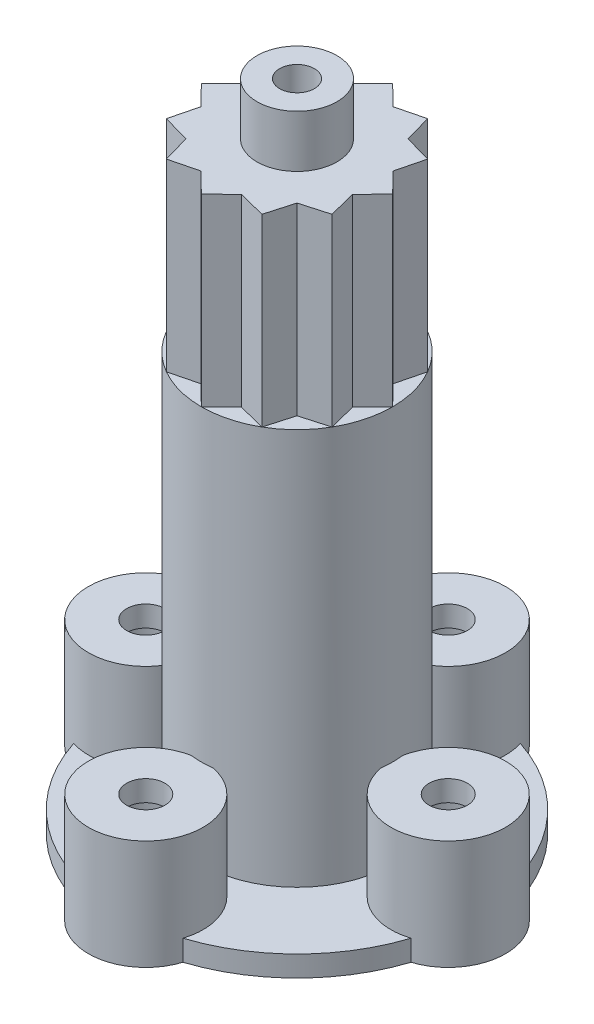
SolidWorks part; units mm, degrees
ref_plane "Front Plane" through (0, 0, 0) normal (0, 0, 1) x (1, 0, 0)
ref_plane "Top Plane" through (0, 0, 0) normal (0, 1, 0) x (1, 0, 0)
ref_plane "Right Plane" through (0, 0, 0) normal (1, 0, 0) x (0, 0, -1)
sketch "Sketch1" plane through (0, 0, 0) normal (0, 1, 0) x (1, 0, 0)
  circle A0 centre (0, 0) radius 10.2
  dimension "D1" = 20.4
extrude "Boss-Extrude1" add sketch "Sketch1" along normal blind 1.2
sketch "Sketch3" plane through (0, 1.2, 0) normal (0, 1, 0) x (1, 0, 0)
  circle A0 centre (0, 0) radius 5.5
  dimension "D1" = 11
extrude "Boss-Extrude2" add sketch "Sketch3" along normal blind 22.8
sketch "Sketch6" plane through (0, 0, 0) normal (0, -1, 0) x (1, 0, 0)
  line L0 (12.265, 0) -> (-12.265, 0) construction
  circle A0 centre (8.7, 0) radius 3.3
  dimension "D1" = 6.6
extrude "Boss-Extrude7" add sketch "Sketch6" against normal blind 6.3 contours A0
ref_axis "Axis1" through (0, 25.2, 0) along (0, -1, 0)
sketch "Sketch7" plane through (0, 0, 0) normal (0, -1, 0) x (1, 0, 0)
  circle A0 centre (8.7, 0) radius 2.2
  dimension "D1" = 4.4
extrude "Cut-Extrude1" cut sketch "Sketch7" against normal blind 5.1
sketch "Sketch8" plane through (0, 6.3, 0) normal (0, 1, 0) x (1, 0, 0)
  circle A0 centre (8.7, 0) radius 1.1
  dimension "D1" = 2.2
extrude "Cut-Extrude2" cut sketch "Sketch8" against normal blind 1.2
pattern_circular "CirPattern1" count 4 over 360 about axis through (0, 25.2, 0) along (0, -1, 0) of "Boss-Extrude7", "Cut-Extrude1", "Cut-Extrude2"
sketch "Sketch9" plane through (0, 0, 0) normal (0, -1, 0) x (-1, 0, 0)
  circle A0 centre (0, 0) radius 4.4
  dimension "D1" = 8.8
extrude "Cut-Extrude3" cut sketch "Sketch9" against normal blind 22.8
sketch "Sketch10" plane through (0, 24, 0) normal (0, 1, 0) x (1, 0, 0)
  circle A0 centre (0, 0) radius 4.5
  dimension "D1" = 9
extrude "Boss-Extrude8" add sketch "Sketch10" along normal blind 10.6
sketch "Sketch11" plane through (0, 24, 0) normal (0, 1, 0) x (1, 0, 0)
  line L0 (-1.2, 4.337) -> (1.2, 4.337)
  line L1 (1.2, 4.337) -> (0, 5.5)
  line L2 (0, 5.5) -> (-1.2, 4.337)
  line L3 (1.2, -4.337) -> (-1.2, -4.337) construction
  line L4 (1.2, -4.337) -> (1.2, 4.337) construction
  line L5 (1.2, 4.337) -> (-1.2, 4.337) construction
  line L6 (-1.2, -4.337) -> (-1.2, 4.337) construction
  line L7 (1.2, -4.337) -> (-1.2, 4.337) construction
  line L8 (1.2, 4.337) -> (-1.2, -4.337) construction
  circle A0 centre (0, 0) radius 4.5 construction
  arc A1 (0.6399, 5.4626) -> (-0.6399, 5.4626) centre (0, 0) ccw construction
  point P4 (0, 0)
  dimension "D1" = 2.4
extrude "Boss-Extrude9" add sketch "Sketch11" along normal blind 10.6 contours L2 L0 L1
pattern_circular "CirPattern2" count 12 over 360 about axis through (0, 25.2, 0) along (0, -1, 0) of "Boss-Extrude9"
sketch "Sketch12" plane through (0, 22.8, 0) normal (0, -1, 0) x (1, 0, 0)
  circle A0 centre (0, 0) radius 3.2
  dimension "D1" = 6.4
extrude "Cut-Extrude4" cut sketch "Sketch12" against normal blind 10.6
sketch "Sketch13" plane through (0, 34.6, 0) normal (0, 1, 0) x (1, 0, 0)
  circle A0 centre (0, 0) radius 2.3
  dimension "D1" = 4.6
extrude "Boss-Extrude10" add sketch "Sketch13" along normal blind 3
sketch "Sketch14" plane through (0, 37.6, 0) normal (0, 1, 0) x (1, 0, 0)
  circle A0 centre (0, 0) radius 1
  dimension "D1" = 2
extrude "Cut-Extrude5" cut sketch "Sketch14" against normal blind 3
sketch "Sketch15" plane through (0, 1.2, 0) normal (0, 1, 0) x (1, 0, 0)
  line L0 (-8.7, 0) -> (0, -8.7) construction
  line L1 (-5.0343, -3.6657) -> (-3.5963, -5.1037)
  line L2 (-5.0343, -3.6657) -> (-5.1861, -3.8174)
  line L3 (-3.5963, -5.1037) -> (-3.748, -5.2554)
  line L4 (-5.1861, -3.8174) -> (-3.748, -5.2554)
extrude "Boss-Extrude11" add sketch "Sketch15" along normal blind 0.1 contours L1 L2 L4 L3
